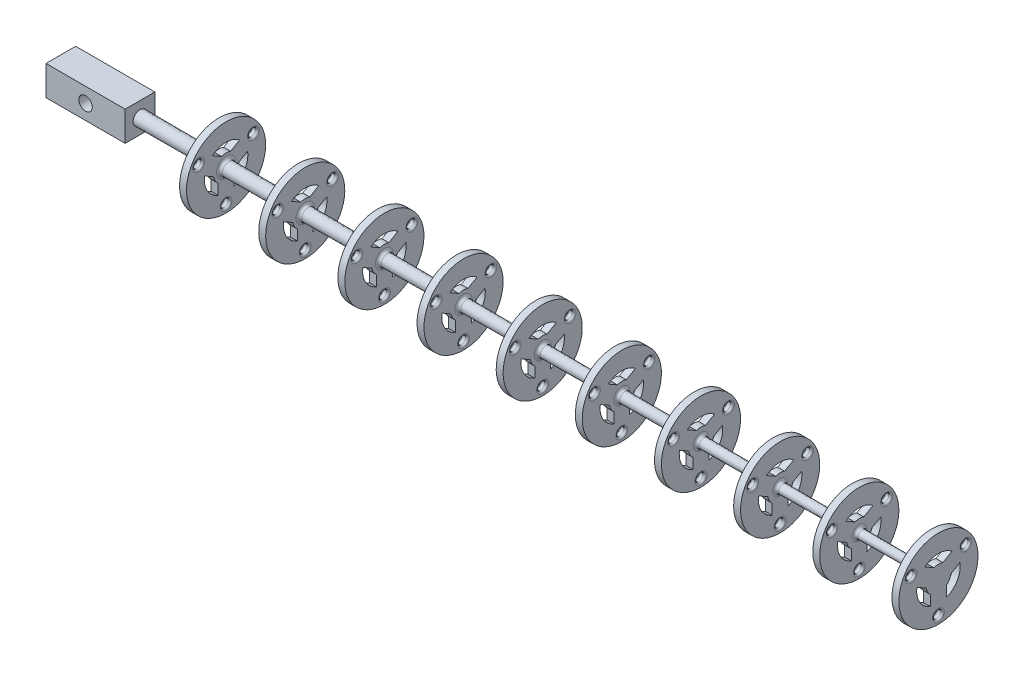
SolidWorks part; units mm, degrees
ref_plane "Front Plane" through (0, 0, 0) normal (0, 0, 1) x (1, 0, 0)
ref_plane "Top Plane" through (0, 0, 0) normal (0, 1, 0) x (1, 0, 0)
ref_plane "Right Plane" through (0, 0, 0) normal (1, 0, 0) x (0, 0, -1)
sketch "Sketch2" plane through (0, 0, 0) normal (0, 0, 1) x (1, 0, 0)
  line L0 (0, 1.75) -> (200, 1)
  line L1 (0, -11) -> (0, 11) construction
  line L2 (200, 1) -> (200, 0)
  line L3 (200, 0) -> (0, 0)
  line L4 (0, 0) -> (0, 1.75)
  dimension "D1" = 1.75
  dimension "D2" = 200
  dimension "D3" = 1
revolve "Revolve1" add sketch "Sketch2" angle 360 about L3
ref_axis "Axis1" through (-3.9062, 0, 0) along (1, 0, 0)
sketch "Sketch3" plane through (0, 0, 0) normal (0, 0, 1) x (1, 0, 0)
  line L0 (20, 0) -> (20, 10)
  line L1 (20, 10) -> (21.75, 10)
  line L2 (21.75, 10) -> (21.75, 0)
  line L3 (21.75, 0) -> (20, 0)
  line L4 (0, -11) -> (0, 11) construction
  dimension "D1" = 1.75
  dimension "D2" = 10
  dimension "D3" = 20
revolve "Revolve2" add sketch "Sketch3" angle 360 about L3
sketch "Sketch5" plane through (21.75, 0, 0) normal (1, 0, 0) x (0, 0, -1)
  line L0 (0, -8) -> (0, 0) construction
  line L1 (0, 0) -> (6.9282, 4) construction
  line L2 (-6.9282, 4) -> (0, 0) construction
  line L3 (0, 11) -> (0, -11) construction
  line L4 (-3.4371, 4.2938) -> (-1.1282, 2.9608)
  line L5 (1.1282, 2.9608) -> (3.4371, 4.2938)
  line L6 (2, -2.4574) -> (2, -5.1235)
  line L7 (5.4371, 0.8297) -> (3.1282, -0.5033)
  line L8 (-3.1282, -0.5033) -> (-5.4371, 0.8297)
  line L9 (-2, -5.1235) -> (-2, -2.4574)
  circle A0 centre (0, -8) radius 1
  circle A1 centre (6.9282, 4) radius 1
  circle A2 centre (-6.9282, 4) radius 1
  arc A3 (-3.4371, 4.2938) -> (3.4371, 4.2938) centre (0, 0) cw
  circle A6 centre (0, 0) radius 10 construction
  arc A8 (-1.1282, 2.9608) -> (1.1282, 2.9608) centre (0, 0) cw
  circle A9 centre (0, 0) radius 1.6684 construction
  arc A10 (5.4371, 0.8297) -> (2, -5.1235) centre (0, 0) cw
  arc A11 (3.1282, -0.5033) -> (2, -2.4574) centre (0, 0) cw
  arc A12 (-2, -5.1235) -> (-5.4371, 0.8297) centre (0, 0) cw
  arc A13 (-2, -2.4574) -> (-3.1282, -0.5033) centre (0, 0) cw
  point P29 (0, 0)
  dimension "D2" = 2
  dimension "D1" = 8
  dimension "D3" = 120
  dimension "D4" = 120
  dimension "D6" = 2
  dimension "D7" = 4.5
  dimension "D5" = 1.5
  dimension "D8" = 3
extrude "Cut-Extrude1" cut sketch "Sketch5" against normal up to next
fillet "Fillet1" radius 0.5 6 edges at (20, 3, -6.9282) (20, -9, 0) (21.75, -7, 0) (21.75, 5, -6.9282) (20, 3, 6.9282) (21.75, 5, 6.9282)
pattern_linear "LPattern1" count 10 spacing 20 along (1, 0, 0) of "Revolve2", "Cut-Extrude1", "Fillet1"
sketch "Sketch16" plane through (0, 0, 0) normal (-1, 0, 0) x (0, 0, 1)
  line L1 (-3.75, -3.75) -> (3.75, -3.75)
  line L2 (-3.75, -3.75) -> (-3.75, 3.75)
  line L3 (-3.75, 3.75) -> (3.75, 3.75)
  line L4 (3.75, -3.75) -> (3.75, 3.75)
  line L5 (-3.75, -3.75) -> (3.75, 3.75) construction
  line L6 (-3.75, 3.75) -> (3.75, -3.75) construction
  point P0 (0, 0)
  dimension "D1" = 7.5
extrude "Boss-Extrude1" add sketch "Sketch16" along normal blind 20
sketch "Sketch19" plane through (0, 0, -3.75) normal (0, 0, -1) x (-1, 0, 0)
  line L0 (3.9062, 0) -> (-200, 0) construction
  line L1 (20, 3.75) -> (0, 3.75) construction
  line L2 (20, 3.75) -> (20, -3.75) construction
  point P0 (10, 0)
  point P7 (10, 3.75)
  point P10 (20, 0)
hole_wizard "M3 Clearance Hole1" positions "Sketch19" profile "Sketch18" hole size "M3" standard "ANSI Metric" end condition through all
sketch "Sketch18" plane through (-10, 0, -3.75) normal (1, 0, 0) x (0, 1, 0)
  line L0 (0, 0) -> (0, 13.75)
  line L1 (0, 13.75) -> (1.7, 13.75)
  line L2 (1.7, 13.75) -> (1.7, 0.025)
  line L3 (1.7, 0.025) -> (1.725, 0)
  line L5 (1.725, 0) -> (0, 0)
  line L6 (-1.7, 0.025) -> (-1.725, 0) construction
  line L11 (0, -6.35) -> (0, 107.95) construction
  dimension "Thru Hole Dia." = 3.4
  dimension "Thru Hole Depth" = 13.75
  dimension "Near C'Sink Dia." = 3.45
  dimension "Near C'Sink Angle" = 90
fillet "Fillet2" radius 0.75 19 edges at (20, -1.675, 0) (21.75, 1.6684, 0) (40, -1.6, 0) (41.75, 1.5934, 0) (60, -1.525, 0) (61.75, 1.5184, 0) (80, -1.45, 0) (81.75, 1.4434, 0) (100, -1.375, 0) (101.75, 1.3684, 0) (120, -1.3, 0) (121.75, 1.2934, 0) (140, -1.225, 0) (141.75, 1.2184, 0) (160, -1.15, 0) (161.75, 1.1434, 0) (180, -1.075, 0) (181.75, 1.0684, 0) (200, 1, 0)
equation "\"R_initial\" = 1.75"
equation "\"D1@Sketch2\"=\"R_initial\""
equation "\"R_distal\" = 1.0"
equation "\"D3@Sketch2\"=\"R_distal\""
equation "\"L\"=200"
equation "\"D2@Sketch2\"=\"L\""
equation "\"disk_thickness\"= 1.75"
equation "\"D1@Sketch3\"=\"disk_thickness\""
equation "\"disk_radius\"= 10"
equation "\"D2@Sketch3\"=\"disk_radius\""
equation "\"disk_spacing_initial\"= 20"
equation "\"D3@Sketch3\"=\"disk_spacing_initial\""
equation "\"tendon_routing_radius\"= 8"
equation "\"D1@Sketch5\"=\"tendon_routing_radius\""
equation "\"tendon_routing_hole_radius\"=2"
equation "\"D2@Sketch5\"=\"tendon_routing_hole_radius\""
equation "\"tendon_routing_hole_fillet\"=0.5"
equation "\"D1@Fillet1\"=\"tendon_routing_hole_fillet\""
equation "\"inter_disk_spacing\"= 20"
equation "\"D3@LPattern1\"=\"inter_disk_spacing\""
equation "\"num_disk\"= 10"
equation "\"D1@LPattern1\"=\"num_disk\""
